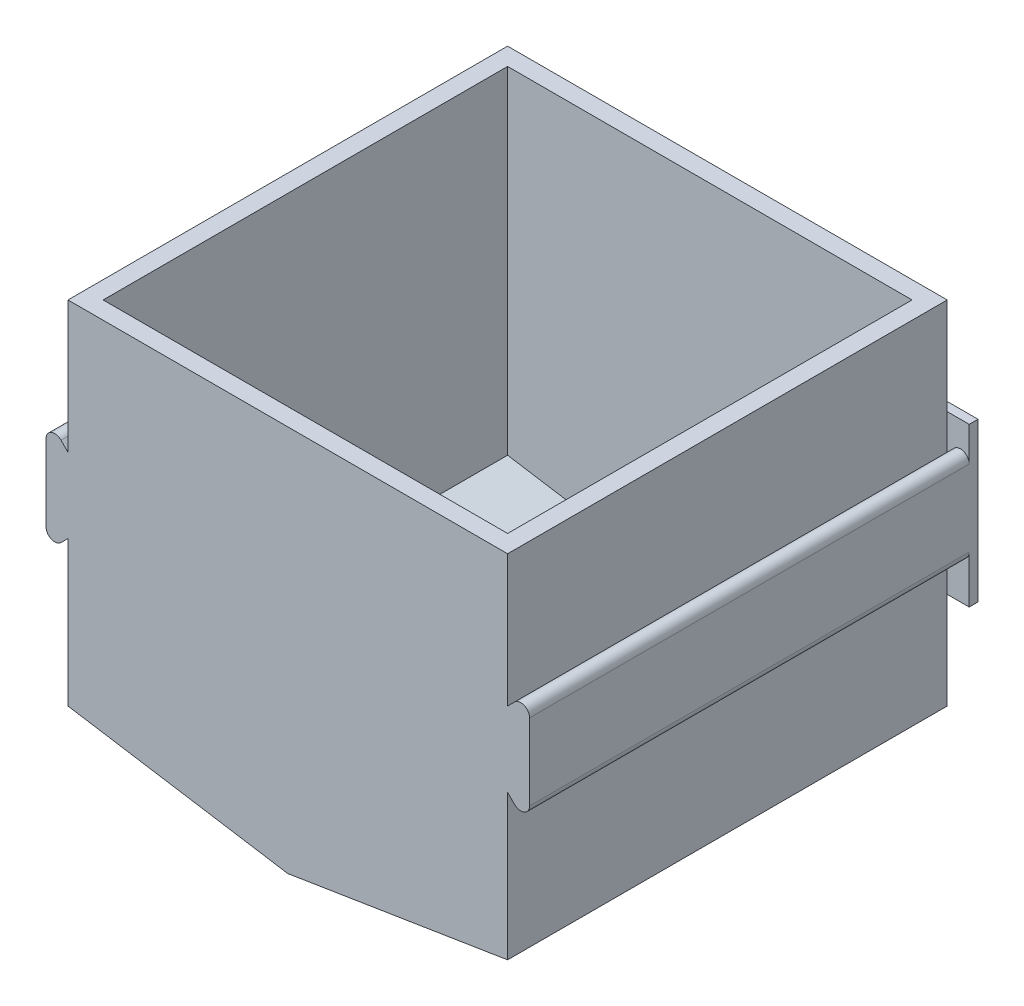
SolidWorks part; units mm, degrees
ref_plane "前视基准面" through (0, 0, 0) normal (0, 0, 1) x (1, 0, 0)
ref_plane "上视基准面" through (0, 0, 0) normal (0, 1, 0) x (1, 0, 0)
ref_plane "右视基准面" through (0, 0, 0) normal (1, 0, 0) x (0, 0, -1)
other "Configuration Table"
sketch "草图2" plane through (0, 0, 0) normal (0, 0, 1) x (1, 0, 0)
  line L0 (-25, -20) -> (0, -24)
  line L2 (-25, -20) -> (-25, 20)
  line L3 (-25, 20) -> (25, 20)
  line L4 (25, -20) -> (25, 20)
  line L5 (-25, -20) -> (25, 20) construction
  line L6 (-25, 20) -> (25, -20) construction
  line L7 (0, -24) -> (25, -20)
  point P0 (0, 0)
  dimension "D1" = 50
  dimension "D2" = 40
  dimension "D3" = 44
extrude "凸台-拉伸1" add sketch "草图2" along normal blind 50
sketch "草图3" plane through (0, 0, 0) normal (0, 0, 1) x (1, 0, 0)
  line L0 (-25, 5) -> (-27.5, 7.5)
  line L1 (-25, 20) -> (-25, -20) construction
  line L2 (-27.5, 7.5) -> (-27.5, -6)
  line L3 (-27.5, -6) -> (-25, -3.5)
  line L4 (-25, -3.5) -> (-25, 5)
  line L5 (0, 20) -> (0, -24) construction
  line L6 (25, 20) -> (-25, 20) construction
  line L8 (27.5, -6) -> (25, -3.5)
  line L9 (27.5, 7.5) -> (27.5, -6)
  line L10 (25, 5) -> (27.5, 7.5)
  line L11 (25, -3.5) -> (25, 5)
  line L12 (-25, 20) -> (-25, -20) construction
  line L13 (0, -24) -> (25, -20) construction
  dimension "D1" = 15
  dimension "D2" = 13.5
  dimension "D3" = 45
  dimension "D4" = 8.5
  dimension "D5" = 45
extrude "凸台-拉伸4" add sketch "草图3" along normal blind 50
shell "抽壳1" thickness 2 removed face at (0, 20, 25)
sketch "草图4" plane through (0, 0, 0) normal (0, 0, -1) x (-1, 0, 0)
  line L1 (-27.5, -9) -> (27.5, -9)
  line L2 (-27.5, -9) -> (-27.5, 9)
  line L3 (-27.5, 9) -> (27.5, 9)
  line L4 (27.5, -9) -> (27.5, 9)
  line L5 (-27.5, -9) -> (27.5, 9) construction
  line L6 (-27.5, 9) -> (27.5, -9) construction
  point P0 (0, 0)
  point P6 (0, 0)
  point P7 (0, 0)
  point P8 (0, 0)
extrude "凸台-拉伸5" add sketch "草图4" along normal blind 1
sketch "草图5" plane through (0, 0, 0) normal (0, 0, 1) x (1, 0, 0)
  line L1 (4, -2) -> (-4, -2)
  line L2 (4, -2) -> (4, 2)
  line L3 (4, 2) -> (-4, 2)
  line L4 (-4, -2) -> (-4, 2)
  line L5 (4, -2) -> (-4, 2) construction
  line L6 (4, 2) -> (-4, -2) construction
  point P0 (0, 0)
  dimension "D1" = 8
  dimension "D2" = 4
extrude "凸台-拉伸6" add sketch "草图5" against normal blind 5
fillet "圆角1" radius 1 4 edges at (27.5, -6, 25) (27.5, 7.5, 25) (-27.5, -6, 25) (-27.5, 7.5, 25)
